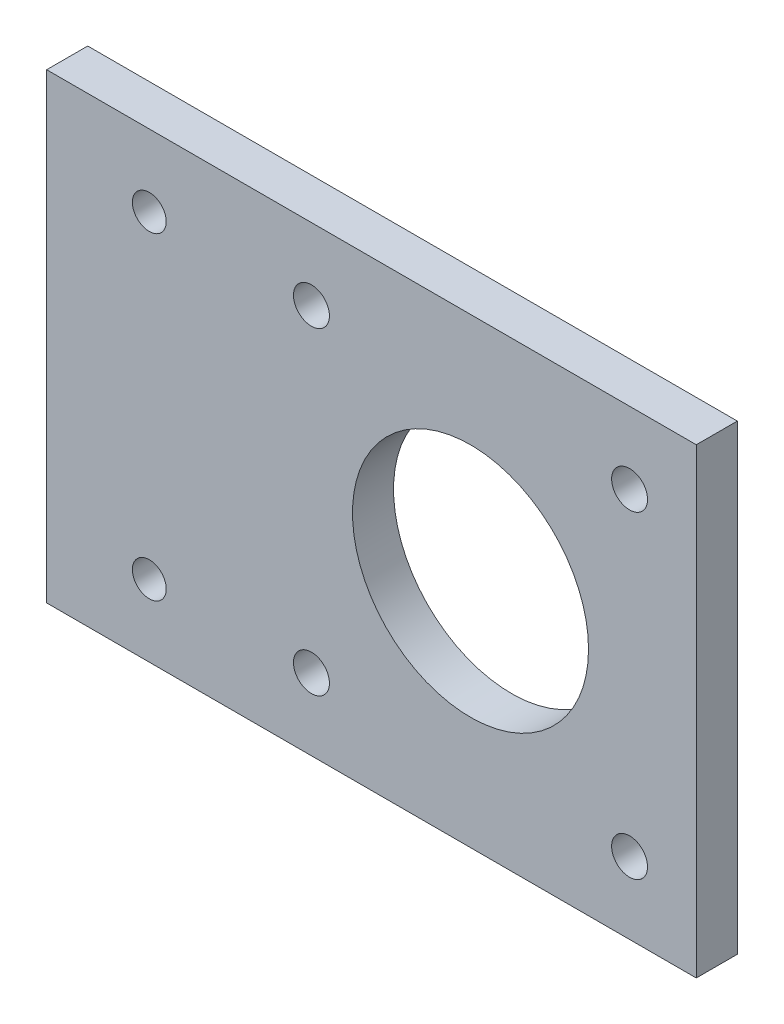
SolidWorks part; units mm, degrees
ref_plane "Plano frontal" through (0, 0, 0) normal (0, 0, 1) x (1, 0, 0)
ref_plane "Plano superior" through (0, 0, 0) normal (0, 1, 0) x (1, 0, 0)
ref_plane "Plano direito" through (0, 0, 0) normal (1, 0, 0) x (0, 0, -1)
sketch "Esboço1" plane through (0, 0, 0) normal (0, 0, 1) x (1, 0, 0)
  line L0 (-41.3, 0) -> (-25.3872, 0) construction
  line L1 (-15.5, 15.5) -> (15.5, 15.5) construction
  line L2 (-15.5, 15.5) -> (-15.5, -15.5) construction
  line L3 (-15.5, -15.5) -> (15.5, -15.5) construction
  line L4 (15.5, 15.5) -> (15.5, -15.5) construction
  line L5 (-15.5, 15.5) -> (15.5, -15.5) construction
  line L6 (-15.5, -15.5) -> (15.5, 15.5) construction
  line L7 (22, 22.5) -> (-41.3, 22.5)
  line L8 (22, 22.5) -> (22, -22.5)
  line L9 (22, -22.5) -> (-41.3, -22.5)
  line L10 (-41.3, 22.5) -> (-41.3, -22.5)
  line L11 (-21.3, -22.5) -> (-21.3, 22.5) construction
  circle A0 centre (0, 0) radius 11.5
  circle A1 centre (-15.5, 15.5) radius 1.75
  circle A2 centre (15.5, 15.5) radius 1.75
  circle A3 centre (15.5, -15.5) radius 1.75
  circle A4 centre (-15.5, -15.5) radius 1.75
  circle A5 centre (-31.3, -15.5) radius 1.65
  circle A6 centre (-31.3, 15.5) radius 1.65
  point P16 (22, 0)
  dimension "D1" = 3.5
  dimension "D2" = 23
  dimension "D7" = 3.3
  dimension "D3" = 31
  dimension "D4" = 45
  dimension "D5" = 22
  dimension "D6" = 21.3
  dimension "D8" = 20
  dimension "D9" = 10
  dimension "D10" = 31
extrude "Ressalto-extrusão1" add sketch "Esboço1" along normal blind 25
sketch "Esboço2" plane through (0, 0, 0) normal (0, 1, 0) x (1, 0, 0)
  line L0 (22, -4) -> (-23, -4)
  line L1 (22, -25) -> (22, 0) construction
  line L2 (-28, -4) -> (-28, -25)
  line L3 (22, -25) -> (-41.3, -25) construction
  line L4 (-23, -25) -> (22, -4)
  line L5 (-41.3, -4) -> (-23, -4)
  line L6 (-41.3, -25) -> (-41.3, 0) construction
  line L8 (22, 0) -> (-41.3, 0) construction
  line L9 (-41.3, -4) -> (-41.3, -25)
  line L10 (-41.3, -25) -> (-23, -25)
  line L11 (-23, -25) -> (22, -25)
  line L12 (22, -25) -> (22, -4)
  dimension "D1" = 4
  dimension "D2" = 45
  dimension "D3" = 5
extrude "Corte-extrusão1" cut sketch "Esboço2" against normal through all both and the other way through all contours L9 L10 L5 | L11 L12 L4 | L2 L10 L4 L0 L5 region at (-11.1818, 0, 11.6364) region at (7, 0, 18) region at (-34.65, 0, 14.5)
